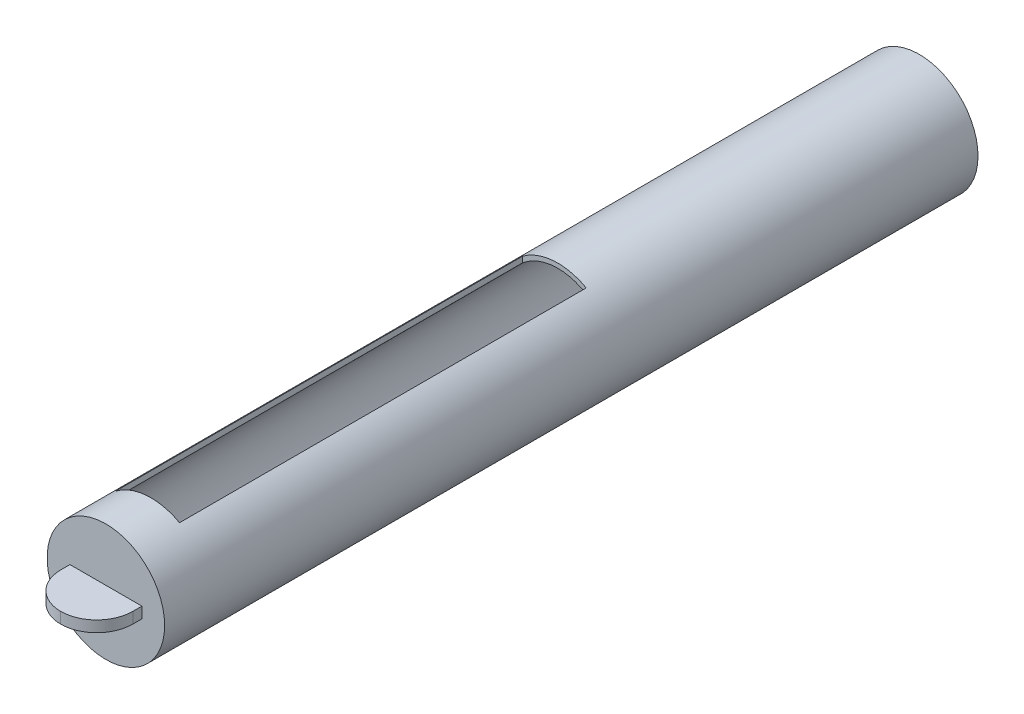
SolidWorks part; units mm, degrees
ref_plane "Front Plane" through (0, 0, 0) normal (0, 0, 1) x (1, 0, 0)
ref_plane "Top Plane" through (0, 0, 0) normal (0, 1, 0) x (1, 0, 0)
ref_plane "Right Plane" through (0, 0, 0) normal (1, 0, 0) x (0, 0, -1)
sketch "Sketch1" plane through (0, 0, 0) normal (0, 0, 1) x (1, 0, 0)
  circle A0 centre (0, -25.4) radius 16.51
  circle A1 centre (0, -25.4) radius 16.51 construction
extrude "Boss-Extrude1" add sketch "Sketch1" along normal blind 12.7 and the other way blind 215.9
shell "Shell1" thickness 1.27
sketch "Sketch2" plane through (0, 0, 0) normal (0, 0, 1) x (1, 0, 0)
  line L1 (7.9949, -4.2134) -> (-9.9493, -4.2134)
  line L2 (7.9949, -4.2134) -> (7.9949, -17.9825)
  line L3 (7.9949, -17.9825) -> (-9.9493, -17.9825)
  line L4 (-9.9493, -4.2134) -> (-9.9493, -17.9825)
extrude "Cut-Extrude1" cut sketch "Sketch2" against normal blind 114.3
sketch "Sketch3" plane through (0, 0, 12.7) normal (0, 0, 1) x (1, 0, 0)
  line L1 (10.1096, -23.8451) -> (-10.1096, -23.8451)
  line L2 (10.1096, -23.8451) -> (10.1096, -26.9549)
  line L3 (10.1096, -26.9549) -> (-10.1096, -26.9549)
  line L4 (-10.1096, -23.8451) -> (-10.1096, -26.9549)
  line L5 (10.1096, -23.8451) -> (-10.1096, -26.9549) construction
  line L6 (10.1096, -26.9549) -> (-10.1096, -23.8451) construction
  point P0 (0, -25.4)
extrude "Boss-Extrude2" add sketch "Sketch3" along normal blind 12.7
fillet "Fillet1" radius 10.16 2 edges at (10.1096, -25.4, 25.4) (-10.1096, -25.4, 25.4)
